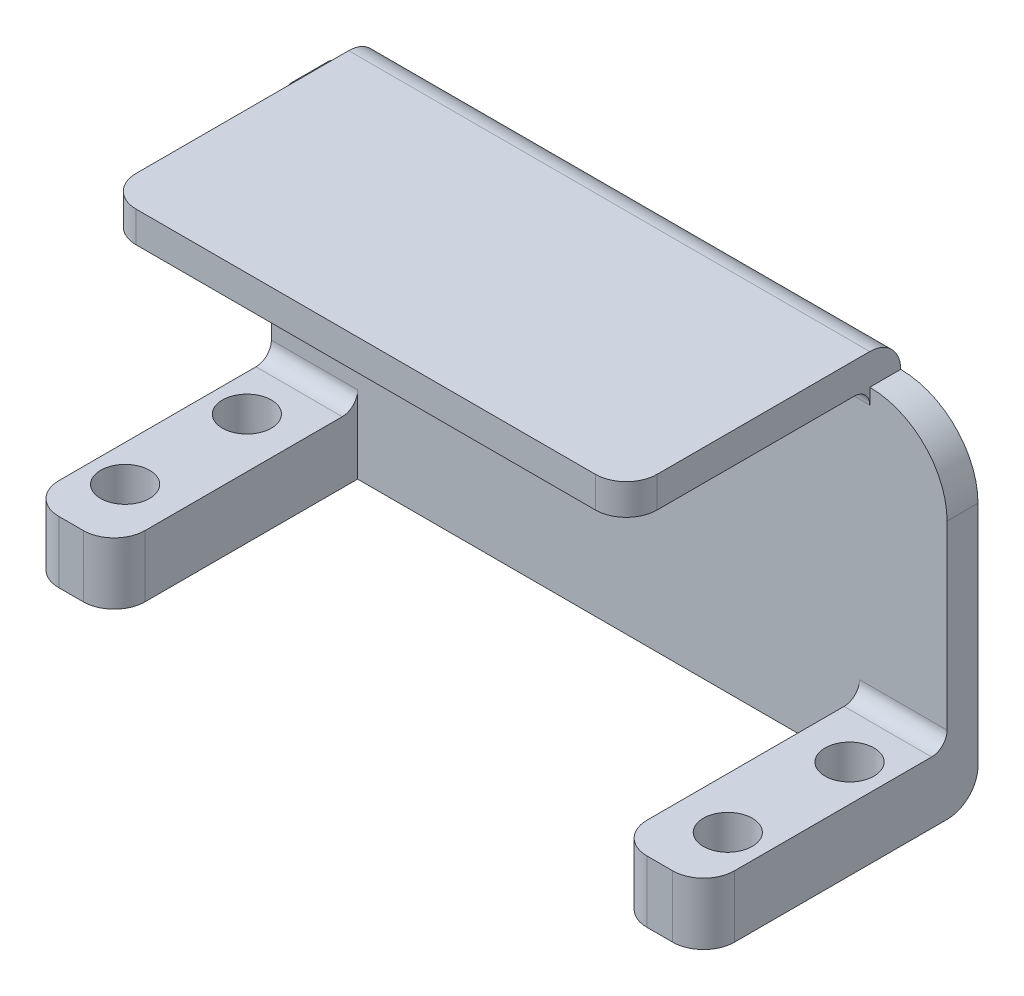
SolidWorks part; units mm, degrees
ref_plane "Front Plane" through (0, 0, 0) normal (0, 0, 1) x (1, 0, 0)
ref_plane "Top Plane" through (0, 0, 0) normal (0, 1, 0) x (1, 0, 0)
ref_plane "Right Plane" through (0, 0, 0) normal (1, 0, 0) x (0, 0, -1)
sketch "Sketch2" plane through (0, 0, 0) normal (0, 0, 1) x (1, 0, 0)
  line L0 (-2.4673, 13.2863) -> (-2.4673, -12.9601) construction
  line L1 (17.5827, 13.2863) -> (-22.5173, 13.2863) construction
  line L2 (-22.5173, -12.9601) -> (17.5827, -12.9601) construction
  line L3 (-22.5173, -2.8051) -> (17.5827, -2.8051) construction
  line L4 (-22.5173, 7.3) -> (-22.5173, -12.9101) construction
  line L5 (17.5827, -12.9101) -> (17.5827, 7.3) construction
  line L6 (-30.2173, -15.9937) -> (-30.2173, -13.0137) construction
  line L7 (25.2827, -13.0137) -> (-30.2173, -13.0137)
  line L8 (25.2827, -13.0137) -> (25.2827, 8.2063)
  line L9 (18.9327, 14.5563) -> (-23.8673, 14.5563)
  line L10 (-30.2173, -13.0137) -> (-30.2173, 8.2063)
  line L12 (-22.6269, -13.0137) -> (-29.2173, -13.0137) construction
  line L13 (-23.8673, 14.5563) -> (-23.8673, 17.0963)
  line L14 (-23.8673, 17.0963) -> (18.9327, 17.0963)
  line L15 (18.9327, 17.0963) -> (18.9327, 14.5563)
  arc A0 (25.2827, 8.2063) -> (18.9327, 14.5563) centre (18.9327, 8.2063) ccw
  arc A1 (-23.8673, 14.5563) -> (-30.2173, 8.2063) centre (-23.8673, 8.2063) ccw
  point P12 (-2.4673, -2.8051)
  point P13 (-2.4673, -2.8051)
  dimension "D3" = 6.35
  dimension "D1" = 1.27
  dimension "D2" = 2.54
extrude "Boss-Extrude1" add sketch "Sketch2" against normal blind 2.54 contours L15 L14 L13 L9 | L9 A1 L10 L7 L8 A0 region at (-2.4673, 0.6298, 0) region at (-2.4673, 15.8263, 0)
sketch "Sketch7" plane through (0, 0, 0) normal (0, 0, 1) x (1, 0, 0)
  line L0 (-30.2173, -13.0137) -> (-30.2173, -7.9337)
  line L1 (-30.2173, -13.0137) -> (-30.2173, 8.2063) construction
  line L2 (-30.2173, -7.9337) -> (-23.1253, -7.9337)
  line L3 (-23.1253, -7.9337) -> (-23.1253, -13.0037)
  line L4 (-29.2173, -13.0037) -> (-22.6273, -13.0037) construction
  line L5 (-23.1253, -13.0037) -> (-30.2173, -13.0137)
  line L7 (-22.6173, -12.9101) -> (-22.6173, 7.3) construction
  line L8 (25.2827, -7.9337) -> (18.0907, -7.9337)
  line L9 (25.2827, -13.0137) -> (25.2827, 8.2063) construction
  line L10 (18.0907, -7.9337) -> (18.0907, -13.0137)
  line L11 (25.2827, -13.0137) -> (-30.2173, -13.0137) construction
  line L12 (18.0907, -13.0137) -> (25.2827, -13.0137)
  line L13 (25.2827, -13.0137) -> (25.2827, -7.9337)
  line L14 (17.5827, -12.9101) -> (17.5827, 7.3) construction
  line L15 (-23.8673, 14.5563) -> (18.9327, 14.5563)
  line L16 (18.9327, 14.5563) -> (18.9327, 17.0963)
  line L17 (18.9327, 17.0963) -> (-23.8673, 17.0963)
  line M5 (18.9327, 14.5563) -> (18.9327, 17.0963)
  line M6 (18.9327, 17.0963) -> (-23.8673, 17.0963)
  line M7 (-23.8673, 17.0963) -> (-23.8673, 14.5563)
  line M9 (-30.2173, 8.2063) -> (-30.2173, -13.0137)
  line M10 (-30.2173, -13.0137) -> (25.2827, -13.0137)
  line M11 (25.2827, -13.0137) -> (25.2827, 8.2063)
  dimension "D1" = 5.08
  dimension "D2" = 0.508
  dimension "D3" = 5.08
  dimension "D4" = 0.508
extrude "Boss-Extrude3" add sketch "Sketch7" along normal up to surface (20 mm away) contours L5 L3 L2 M9 | L8 L10 M10 M11 | L15 M7 M5 M6 region at (-26.6725, -10.4712, 0) region at (21.6867, -10.4737, 0) region at (-2.4673, 15.8263, 0)
fillet "Fillet3" radius 2.54 8 edges at (-2.4673, 17.0963, -2.54) (18.9327, 15.8263, 20) (-23.8673, 15.8263, 20) (-2.4673, -13.0137, -2.54) (18.0907, -10.4737, 20) (25.2827, -10.4737, 20) (-23.1253, -10.4687, 20) (-30.2173, -10.4737, 20)
fillet "Fillet4" radius 1.27 3 edges at (21.6867, -7.9337, 0) (-26.6713, -7.9337, 0) (-2.4673, 14.5563, 0)
sketch "Sketch8" plane through (0.0183, -12.9711, 0) normal (0.0014, -1, 0) x (1, 0.0014, 0)
  circle A1 centre (-27.2399, 5) radius 2.01
  circle A2 centre (-27.2399, 5) radius 2.01
  circle A3 centre (22.2601, 5) radius 2.01
  circle A4 centre (22.2601, 5) radius 2.01
  circle A5 centre (22.2601, 15) radius 2.01
  circle A6 centre (22.2601, 15) radius 2.01
  circle A7 centre (-27.2399, 15) radius 2.01
  circle A8 centre (-27.2399, 15) radius 2.01
  dimension "D1" = 0
  dimension "D2" = 0
  dimension "D3" = 0
  dimension "D4" = 0
extrude "Cut-Extrude2" cut sketch "Sketch8" against normal up to surface and the other way up to surface up to face at (-26.6713, -7.9337, 13.0854) other way up to face at (21.6867, -13.0137, 12.662)
ref_axis "Axis1" through (0, 0, 21.127) along (0, 0, -1)
